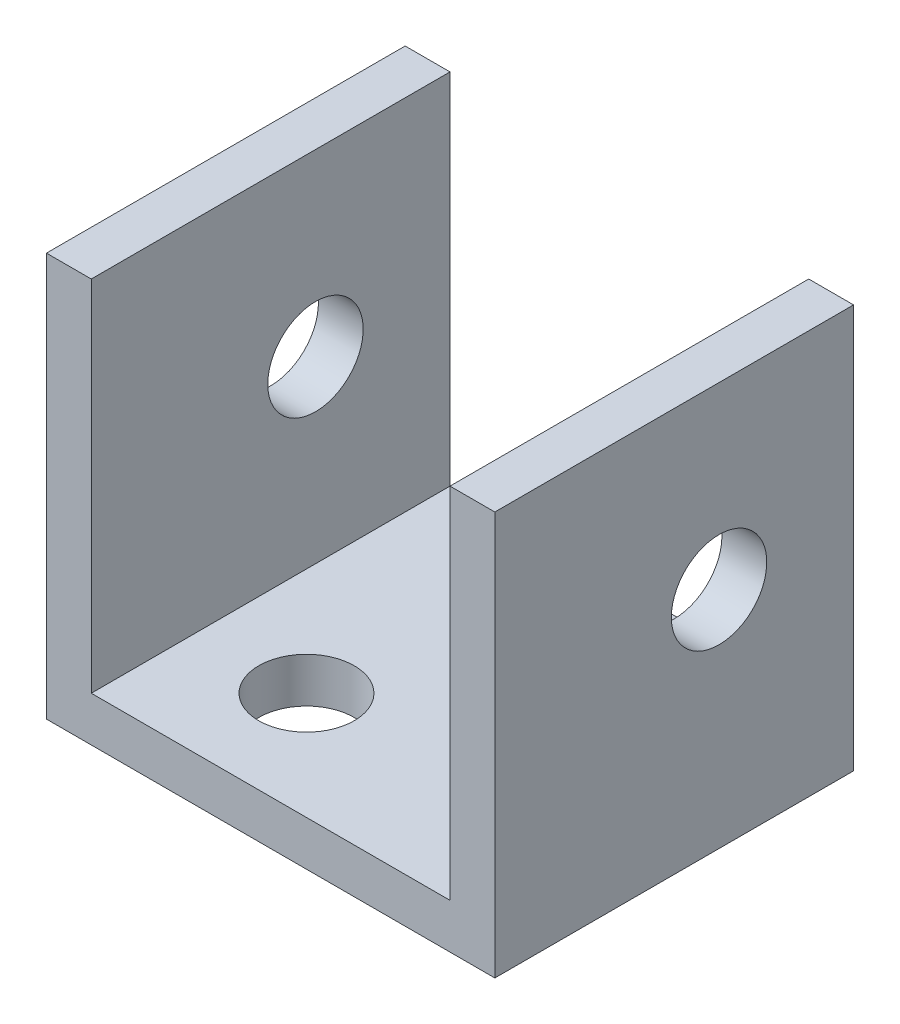
SolidWorks part; units mm, degrees
material "6061-T6 (SS)"
ref_plane "Front" through (0, 0, 0) normal (0, 0, 1) x (1, 0, 0)
ref_plane "Top" through (0, 0, 0) normal (0, 1, 0) x (1, 0, 0)
ref_plane "Right" through (0, 0, 0) normal (1, 0, 0) x (0, 0, -1)
sketch "Sketch1" plane through (0, 0, 0) normal (0, 1, 0) x (1, 0, 0)
  line L1 (-15.875, -12.7) -> (15.875, -12.7)
  line L2 (-15.875, -12.7) -> (-15.875, 12.7)
  line L3 (-15.875, 12.7) -> (15.875, 12.7)
  line L4 (15.875, -12.7) -> (15.875, 12.7)
  line L5 (-15.875, -12.7) -> (15.875, 12.7) construction
  line L6 (-15.875, 12.7) -> (15.875, -12.7) construction
  point P0 (0, 0)
  dimension "D1" = 31.75
  dimension "D2" = 25.4
extrude "Boss-Extrude1" add sketch "Sketch1" along normal blind 3.175
sketch "Sketch2" plane through (0, 3.175, 0) normal (0, 1, 0) x (1, 0, 0)
  line L0 (-15.875, 12.7) -> (-15.875, -12.7)
  line L1 (-15.875, -12.7) -> (-12.7, -12.7)
  line L2 (-15.875, -12.7) -> (15.875, -12.7) construction
  line L3 (-12.7, -12.7) -> (-12.7, 12.7)
  line L4 (15.875, 12.7) -> (-15.875, 12.7) construction
  line L5 (-12.7, 12.7) -> (-15.875, 12.7)
  line L6 (15.875, 12.7) -> (12.7, 12.7)
  line L7 (12.7, 12.7) -> (12.7, -12.7)
  line L8 (12.7, -12.7) -> (15.875, -12.7)
  line L9 (15.875, -12.7) -> (15.875, 12.7)
  dimension "D1" = 3.175
extrude "Boss-Extrude2" add sketch "Sketch2" along normal blind 25.4
sketch "Sketch6" plane through (0, 3.175, 0) normal (0, 1, 0) x (1, 0, 0)
  line L0 (12.7, 12.7) -> (-12.7, 12.7) construction
  line L1 (12.7, 12.7) -> (12.7, -12.7) construction
  line L2 (-12.7, -12.7) -> (-12.7, 12.7) construction
  line L3 (-12.7, -12.7) -> (12.7, -12.7) construction
  point P0 (5.08, 5.08)
  point P2 (-5.08, -5.08)
  dimension "D1" = 7.62
  dimension "D2" = 7.62
  dimension "D3" = 7.62
  dimension "D4" = 7.62
hole_wizard "1/4 Clearance Hole2" positions "Sketch6" profile "Sketch5" hole size "1/4" standard "ANSI Inch" end condition through all
sketch "Sketch5" plane through (5.08, 3.175, -5.08) normal (1, 0, 0) x (0, 0, 1)
  line L0 (0, 0) -> (0, 3.175)
  line L1 (0, 3.175) -> (3.3782, 3.175)
  line L2 (3.3782, 3.175) -> (3.3782, 0)
  line L5 (3.3782, 0) -> (0, 0)
  line L11 (0, -6.35) -> (0, 107.95) construction
  dimension "Thru Hole Dia." = 6.7564
  dimension "Thru Hole Depth" = 3.175
sketch "Sketch9" plane through (-15.875, 0, 0) normal (-1, 0, 0) x (0, 0, 1)
  line L0 (-12.7, 28.575) -> (12.7, 28.575) construction
  line L1 (-12.7, 28.575) -> (-12.7, 0) construction
  point P0 (-3.175, 15.875)
  dimension "D1" = 12.7
  dimension "D2" = 9.525
hole_wizard "1/4 Clearance Hole1" positions "Sketch9" profile "Sketch8" hole size "1/4" standard "ANSI Inch" end condition through all
sketch "Sketch8" plane through (-15.875, 15.875, -3.175) normal (0, 1, 0) x (0, 0, 1)
  line L0 (0, 0) -> (0, 31.75)
  line L1 (0, 31.75) -> (3.3782, 31.75)
  line L2 (3.3782, 31.75) -> (3.3782, 0)
  line L5 (3.3782, 0) -> (0, 0)
  line L11 (0, -6.35) -> (0, 107.95) construction
  dimension "Thru Hole Dia." = 6.7564
  dimension "Thru Hole Depth" = 31.75
